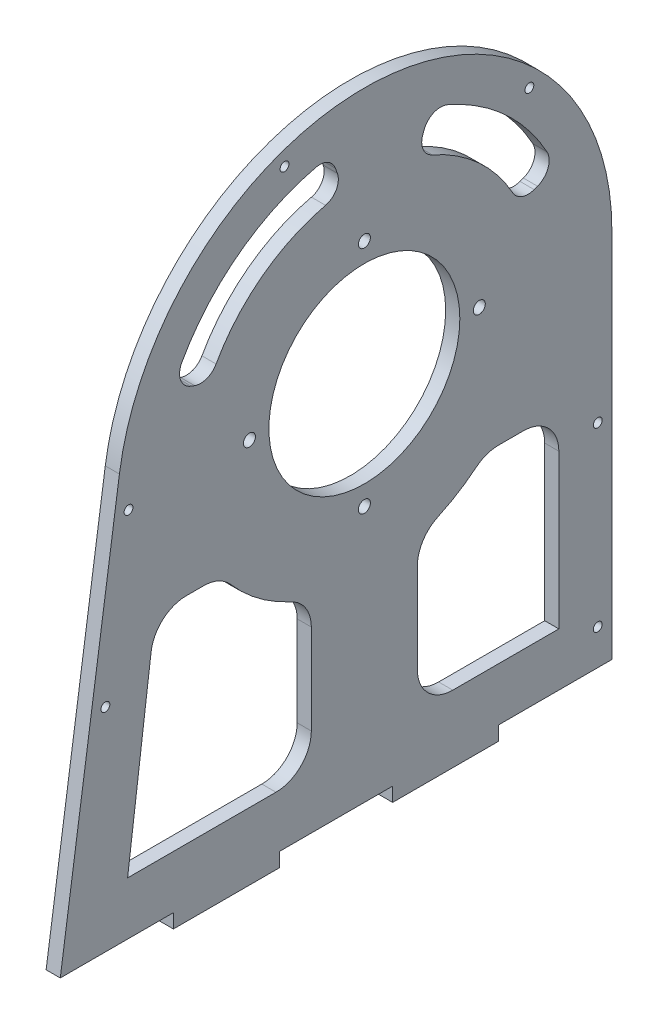
SolidWorks part; units mm, degrees
ref_plane "Ebene vorne" through (0, 0, 0) normal (1, 0, 0) x (0, 1, 0)
ref_plane "Ebene oben" through (0, 0, 0) normal (0, 0, 1) x (0, 1, 0)
ref_plane "Ebene rechts" through (0, 0, 0) normal (0, 1, 0) x (-1, 0, 0)
sketch "Skizze2" plane through (0, 0, 0) normal (1, 0, 0) x (0, 0, -1)
  line L0 (-10.4961, -82.1889) -> (-151.2319, -82.1889) construction
  line L1 (-10.4961, -82.1889) -> (-10.4961, -187.1889)
  line L2 (-80.4961, -12.1889) -> (-80.4961, -187.1889) construction
  line L3 (-10.4961, -187.1889) -> (-166.4961, -187.1889)
  line L4 (-80.4961, -12.1889) -> (-80.4961, -82.1889) construction
  line L5 (-107.4961, -82.1889) -> (-112.9961, -82.1889)
  line L6 (-80.4961, -55.1889) -> (-80.4961, -49.6889)
  line L7 (-53.4961, -82.1889) -> (-47.9961, -82.1889)
  line L8 (-80.4961, -109.1889) -> (-80.4961, -114.6889)
  line L9 (-80.4961, -12.1889) -> (-80.4961, -16.1889)
  line L10 (-10.4961, -82.1889) -> (-14.4961, -82.1889)
  line L11 (-151.2319, -82.1889) -> (-147.1898, -82.1889) construction
  line L12 (-14.4961, -82.1889) -> (-14.4961, -187.1889) construction
  line L13 (-14.4961, -187.1889) -> (-14.4961, -177.1889) construction
  line L14 (-14.4961, -82.1889) -> (-14.4961, -127.1889) construction
  line L15 (-25.4961, -172.1889) -> (-55.4961, -172.1889)
  line L16 (-130.8778, -111.3991) -> (-125.9114, -111.3991)
  line L17 (-35.4961, -118.6717) -> (-42.5574, -118.6717)
  line L18 (-95.4961, -146.4617) -> (-95.4961, -136.7324)
  line L19 (-65.4961, -146.4617) -> (-65.4961, -136.7324)
  line L20 (-14.4961, -82.1889) -> (-14.4961, -127.1889) construction
  line L21 (-166.4961, -187.1889) -> (-149.7679, -72.1186)
  line L22 (-162.5377, -187.7643) -> (-145.8096, -72.694) construction
  line L23 (-80.4961, -82.1889) -> (-30.9986, -32.6914) construction
  line L24 (-140.797, -120.1305) -> (-147.4554, -172.1889)
  line L25 (-147.4554, -172.1889) -> (-135.4957, -172.1889)
  line L26 (-80.4961, -82.1889) -> (-103.0694, -20.1692) construction
  line L27 (-25.4961, -128.6717) -> (-25.4961, -172.1889)
  line L29 (-80.4961, -182.1889) -> (-80.4961, -140.4389)
  line L31 (-65.4961, -162.1889) -> (-65.4961, -146.4617)
  line L33 (-80.4961, -182.1889) -> (-80.4961, -137.0089)
  line L35 (-95.4961, -162.1889) -> (-95.4961, -146.4617)
  line L36 (-105.4961, -172.1889) -> (-135.4957, -172.1889)
  arc A0 (-10.4961, -82.1889) -> (-149.7679, -72.1186) centre (-80.4961, -82.1889) ccw
  circle A1 centre (-80.4961, -82.1889) radius 27
  circle A2 centre (-80.4961, -82.1889) radius 27
  circle A4 centre (-147.1898, -82.1889) radius 1.25
  circle A5 centre (-14.4961, -82.1889) radius 2.7068
  circle A7 centre (-47.9961, -82.1889) radius 1.65
  circle A8 centre (-33.827, -35.5198) radius 1.2509
  arc A10 (-14.4961, -82.1889) -> (-145.8096, -72.694) centre (-80.4961, -82.1889) ccw construction
  arc A11 (-118.3422, -114.8641) -> (-101.3294, -127.6418) centre (-80.4961, -82.1889) ccw
  arc A12 (-59.6628, -127.6418) -> (-48.8805, -120.9246) centre (-80.4961, -82.1889) ccw
  arc A13 (-25.4961, -128.6717) -> (-35.4961, -118.6717) centre (-35.4961, -128.6717) ccw
  arc A14 (-48.8805, -120.9246) -> (-42.5574, -118.6717) centre (-42.5574, -128.6717) cw
  arc A15 (-65.4961, -136.7324) -> (-59.6628, -127.6418) centre (-55.4961, -136.7324) cw
  arc A16 (-95.4961, -136.7324) -> (-101.3294, -127.6418) centre (-105.4961, -136.7324) ccw
  arc A17 (-125.9114, -111.3991) -> (-118.3422, -114.8641) centre (-125.9114, -121.3991) cw
  arc A18 (-140.797, -120.1305) -> (-130.8778, -111.3991) centre (-130.8778, -121.3991) cw
  arc A19 (-55.4961, -172.1889) -> (-65.4961, -162.1889) centre (-55.4961, -162.1889) cw
  arc A20 (-105.4961, -172.1889) -> (-95.4961, -162.1889) centre (-105.4961, -162.1889) ccw
  circle A21 centre (-80.4961, -82.1889) radius 37.5 construction
  point P67 (-65.4961, -129.8858)
  dimension "D1" = 4
  dimension "D3" = 10
  dimension "D4" = 10
  dimension "D5" = 4
  dimension "D2" = 70
  dimension "D6" = 54
  dimension "D8" = 45
  dimension "D12" = 105
  dimension "D7" = 156
  dimension "D9" = 20
  dimension "D10" = 60
  dimension "D11" = 10
extrude "Aufsatz-Linear austragen3" add sketch "Skizze2" along normal blind 4 contours L1 L3 L21 A0
extrude "Schnitt-Linear austragen5" cut sketch "Skizze2<24>" against normal blind 9.5 and the other way blind 9.5 contours A1
sketch "Skizze2<24>" plane through (0, 0, 0) normal (1, 0, 0) x (0, 0, -1) same geometry as "Skizze2"
hole_wizard "Durchgangsloch für M31" positions "Skizze8" profile "Skizze9" hole size "M3" standard "DIN"
sketch "Skizze8" plane through (0, 0, 0) normal (-1, 0, 0) x (0, 0, 1)
  point P0 (47.9961, -82.1889)
  point P3 (80.4961, -49.6889)
  point P6 (112.9961, -82.1889)
  point P9 (80.4961, -114.6889)
sketch "Skizze9" plane through (0, -82.1889, 47.9961) normal (0, 1, 0) x (0, 0, 1)
  line L0 (0, 0) -> (0, 21.0215)
  line L1 (0, 21.0215) -> (1.7, 20)
  line L2 (1.7, 20) -> (1.7, 0)
  line L5 (1.7, 0) -> (0, 0)
  line L10 (0, 21.0215) -> (-1.7, 20) construction
  line L11 (0, -6.35) -> (0, 107.95) construction
  dimension "Bohrerdurchmesser" = 3.4
  dimension "Bohrungstiefe" = 20
  dimension "Spitzenwinkel" = 118
hole_wizard "M3 Gewindebohrung1" positions "Skizze10" profile "Skizze11" tap size "M3" standard "DIN"
sketch "Skizze10" plane through (0, 0, 0) normal (-1, 0, 0) x (0, 0, 1)
  line L0 (162.5377, -187.7643) -> (145.8096, -72.694) construction
  line L4 (80.4961, -82.1889) -> (103.0694, -20.1692) construction
  line L6 (10.4961, -187.1889) -> (166.4961, -187.1889) construction
  line L9 (151.2319, -82.1889) -> (10.4961, -82.1889) construction
  line L10 (166.4961, -187.1889) -> (149.7679, -72.1186) construction
  line L12 (80.864, -82.1889) -> (80.5892, -12.1889) construction
  line L14 (80.864, -82.1889) -> (33.827, -35.5198) construction
  line L16 (80.864, -82.1889) -> (104.5046, -16.4348) construction
  line L18 (10.4961, -187.1889) -> (166.4961, -187.1889) construction
  arc A0 (145.8096, -72.694) -> (14.4961, -82.1889) centre (80.4961, -82.1889) ccw construction
  arc A1 (149.7679, -72.1186) -> (10.4961, -82.1889) centre (80.4961, -82.1889) ccw construction
  circle A3 centre (80.4961, -82.1889) radius 66 construction
  point P0 (33.827, -35.5198)
  point P3 (103.0694, -20.1692)
  point P18 (14.4961, -127.1889)
  point P21 (14.4961, -177.1889)
  point P26 (147.1898, -82.1889)
  point P50 (153.7316, -127.1889)
  dimension "D7" = 4
  dimension "D1" = 60
  dimension "D2" = 20
  dimension "D3" = 45
  dimension "D5" = 10
  dimension "D6" = 60
sketch "Skizze11" plane through (0, -35.5198, 33.827) normal (0, 1, 0) x (0, 0, 1)
  line L0 (0, 0) -> (0, 9.2511)
  line L1 (0, 9.2511) -> (1.25, 8.5)
  line L2 (1.25, 8.5) -> (1.25, 0)
  line L5 (1.25, 0) -> (0, 0)
  line L10 (0, 9.2511) -> (-1.25, 8.5) construction
  line L11 (0, -6.35) -> (0, 107.95) construction
  dimension "Bohrerdurchmesser" = 2.5
  dimension "Bohrungstiefe" = 8.5
  dimension "Spitzenwinkel" = 118
extrude "Schnitt-Linear austragen6" cut sketch "Skizze2<28>" along normal blind 11.5 contours L15 A19 L31 L19 A15 A12 A14 L17 A13 L27 | L36 L25 L24 A18 L16 A17 A11 A16 L18 L35 A20
sketch "Skizze2<28>" plane through (0, 0, 0) normal (1, 0, 0) x (0, 0, -1) same geometry as "Skizze2"
sketch "Skizze12" plane through (0, 0, 0) normal (-1, 0, 0) x (0, -1, 0)
  line L1 (31.9125, 63.9738) -> (30.971, 63.6311)
  line L2 (29.2869, 88.1383) -> (27.761, 88.6937)
  line L4 (12.1889, 80.4961) -> (187.1889, 80.4961) construction
  line L5 (61.1065, 128.5133) -> (60.7602, 129.4648)
  line L7 (187.1889, 10.4961) -> (187.1889, 166.4961) construction
  line L9 (61.1065, 32.4789) -> (60.7602, 31.5274)
  arc A0 (58.8402, 122.4346) -> (35.4614, 91.4753) centre (82.1889, 80.4961) ccw
  arc A1 (53.6426, 132.1305) -> (24.801, 94.1939) centre (82.1889, 80.4961) ccw
  arc A2 (38.2044, 61.2773) -> (58.8402, 38.5576) centre (82.1889, 80.4961) ccw
  arc A3 (28.0971, 56.936) -> (53.6426, 28.8617) centre (82.1889, 80.4961) ccw
  arc A6 (31.9125, 63.9738) -> (38.2044, 61.2773) centre (33.6226, 59.2753) cw
  arc A7 (30.971, 63.6311) -> (28.0971, 56.936) centre (32.6811, 58.9326) ccw
  arc A10 (29.2869, 88.1383) -> (35.4614, 91.4753) centre (30.8922, 92.5488) ccw
  arc A11 (27.761, 88.6937) -> (24.801, 94.1939) centre (29.3663, 93.1042) cw
  circle A14 centre (82.1889, 80.4961) radius 27 construction
  arc A15 (58.8402, 122.4346) -> (61.1065, 128.5133) centre (56.4081, 126.8032) ccw
  arc A16 (53.6426, 132.1305) -> (60.7602, 129.4648) centre (56.0618, 127.7547) cw
  arc A18 (53.6426, 28.8617) -> (60.7602, 31.5274) centre (56.0618, 33.2375) ccw
  arc A19 (58.8402, 38.5576) -> (61.1065, 32.4789) centre (56.4081, 34.189) cw
  point P13 (82.1889, 21.8894)
  point P16 (81.4799, 32.8894)
  point P19 (36.5399, 65.658)
  point P22 (26.1982, 61.8939)
  point P25 (82.1889, 139.8894)
  dimension "D2" = 96
  dimension "D1" = 118
  dimension "D7" = 5
  dimension "D8" = 5
  dimension "D9" = 48
  dimension "D10" = 5
  dimension "D3" = 20
  dimension "D4" = 20
  dimension "D6" = 20
  dimension "D5" = 20
extrude "Schnitt-Linear austragen7" cut sketch "Skizze12" against normal through all
mirror "Spiegeln1" about plane through (4, -82.1889, 80.4961) normal (1, 0, 0) of bodies 115
delete or keep bodies "Körper-Löschen/beibehalten 1" type delete bodies bodies 115
sketch "Skizze13" plane through (0, -187.1889, 0) normal (0, -1, 0) x (1, 0, 0)
  line L0 (4, 10.4961) -> (4, 166.4961) construction
  line L5 (8, 10.4961) -> (8, 166.4961) construction
  line L6 (4, 42.4961) -> (8, 42.4961)
  line L7 (4, 42.4961) -> (4, 72.4961)
  line L8 (4, 72.4961) -> (8, 72.4961)
  line L9 (8, 42.4961) -> (8, 72.4961)
  line L11 (4, 166.4961) -> (8, 166.4961) construction
  line L12 (4, 134.4961) -> (8, 134.4961)
  line L13 (4, 134.4961) -> (4, 104.4961)
  line L14 (4, 104.4961) -> (8, 104.4961)
  line L15 (8, 134.4961) -> (8, 104.4961)
  line L16 (4, 10.4961) -> (8, 10.4961) construction
  dimension "D1" = 30
  dimension "D2" = 30
  dimension "D3" = 32
  dimension "D4" = 32
extrude "Aufsatz-Linear austragen4" add sketch "Skizze13" along normal blind 4
equation "\"D4@Skizze12\"=\"D3@Skizze12\""
